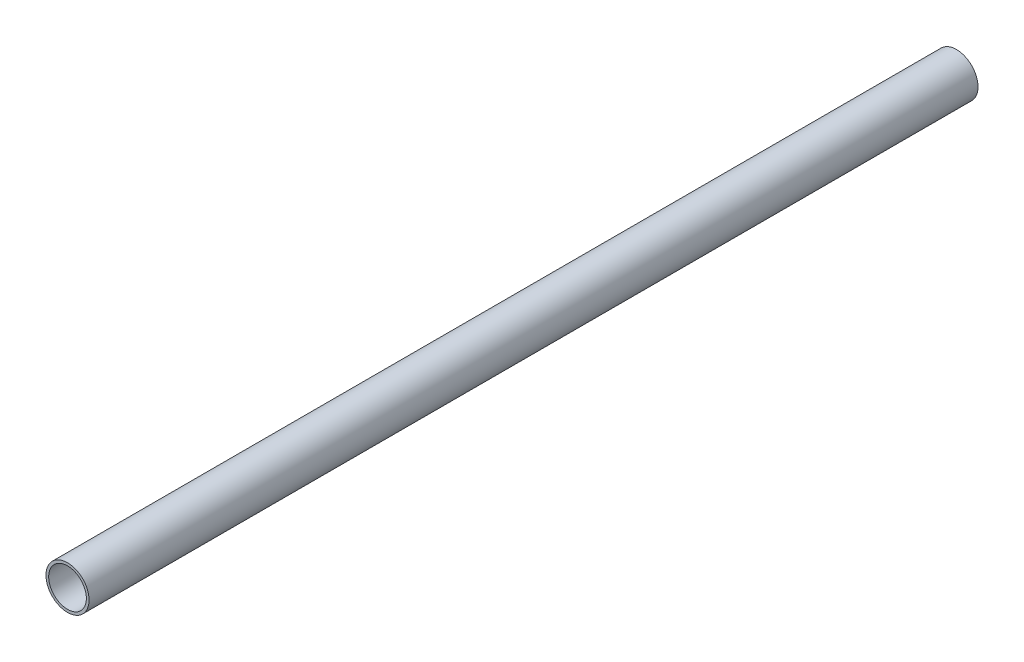
SolidWorks part; units mm, degrees
material "Thornel Mat VMA"
ref_plane "Спереди" through (0, 0, 0) normal (0, 0, 1) x (1, 0, 0)
ref_plane "Сверху" through (0, 0, 0) normal (0, 1, 0) x (1, 0, 0)
ref_plane "Справа" through (0, 0, 0) normal (1, 0, 0) x (0, 0, -1)
sketch "Эскиз1" plane through (0, 0, 0) normal (0, 0, 1) x (1, 0, 0)
  circle A0 centre (0, 0) radius 7
  circle A1 centre (0, 0) radius 8
  dimension "D1" = 14
  dimension "D2" = 1
sketch "Эскиз2" plane through (0, 0, 0) normal (0, 0, 1) x (1, 0, 0)
  circle A2 centre (0, 0) radius 8
  circle A3 centre (0, 0) radius 8
  dimension "D1" = 1
extrude "Бобышка-Вытянуть2" add sketch "Эскиз1" along normal blind 165 and the other way blind 165 contours A0 | A1
